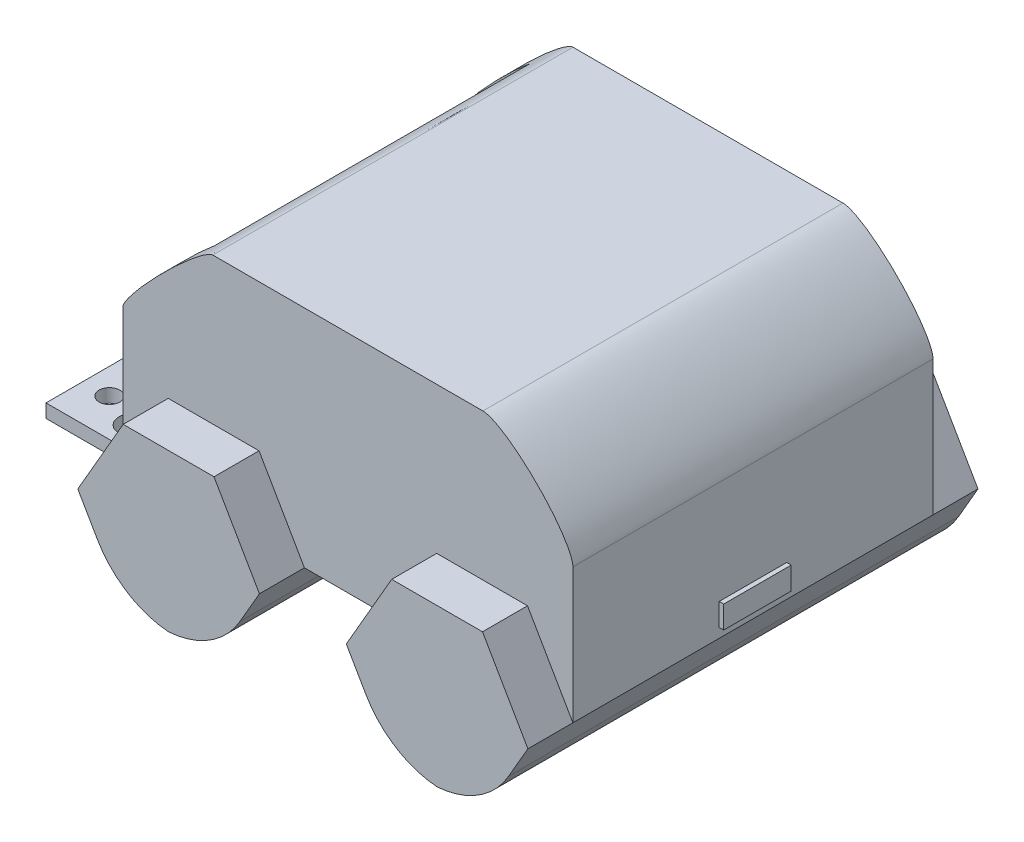
SolidWorks part; units mm, degrees
ref_plane "前基準面" through (0, 0, 0) normal (0, 0, 1) x (1, 0, 0)
ref_plane "上基準面" through (0, 0, 0) normal (0, 1, 0) x (1, 0, 0)
ref_plane "右基準面" through (0, 0, 0) normal (1, 0, 0) x (0, 0, -1)
sketch "草圖1" plane through (0, 0, 0) normal (0, 1, 0) x (1, 0, 0)
  line L1 (-50, 40) -> (50, 40)
  line L2 (-50, 40) -> (-50, -40)
  line L3 (-50, -40) -> (50, -40)
  line L4 (50, 40) -> (50, -40)
  line L5 (-50, 40) -> (50, -40) construction
  line L6 (-50, -40) -> (50, 40) construction
  point P0 (0, 0)
  dimension "D1" = 100
  dimension "D2" = 80
extrude "填料-伸長1" add sketch "草圖1" along normal blind 50
sketch "草圖4" plane through (0, 0, 40) normal (0, 0, 1) x (1, 0, 0)
  line L0 (-50, 0) -> (50, 0) construction
  line L1 (50, 0) -> (39.9127, 17.4718)
  line L2 (39.9127, 17.4718) -> (19.738, 17.4718)
  line L3 (19.738, 17.4718) -> (9.6507, 0)
  line L4 (9.6507, 0) -> (19.738, -17.4718)
  line L5 (19.738, -17.4718) -> (39.9127, -17.4718)
  line L6 (39.9127, -17.4718) -> (50, 0)
  circle A0 centre (29.8253, 0) radius 17.4718 construction
extrude "填料-伸長3" add sketch "草圖4" against normal blind 90 and the other way blind 10
fillet "圓角1" radius 20 1 edges at (50, 50, 0) conic rho 0.2
fillet "圓角2" radius 20 2 edges at (39.9127, -17.4718, 0) (19.738, -17.4718, 0)
sketch "草圖7" plane through (50, 0, 0) normal (1, 0, 0) x (0, 0, -1)
  line L0 (0, -1000) -> (0, 49000) construction
  line L1 (-40, 0) -> (40, 0) construction
  line L3 (-7.5, 7.0981) -> (7.5, 7.0981)
  line L4 (-7.5, 7.0981) -> (-7.5, 2.0981)
  line L5 (-7.5, 2.0981) -> (7.5, 2.0981)
  line L6 (7.5, 7.0981) -> (7.5, 2.0981)
  line L7 (-7.5, 7.0981) -> (7.5, 2.0981) construction
  line L8 (-7.5, 2.0981) -> (7.5, 7.0981) construction
  point P1 (0, 4.5981)
  point P5 (0, 0)
  dimension "D1" = 15
  dimension "D2" = 5
extrude "填料-伸長4" add sketch "草圖7" along normal blind 1
sketch "草圖8" plane through (0, 0, 40) normal (0, 0, 1) x (1, 0, 0)
  line L0 (9.6507, 0) -> (50, 0) construction
  line L1 (50, 30) -> (50, 0) construction
  line L2 (50, 0) -> (39.9127, 17.4718) construction
  line L3 (-50, 0) -> (-9.65, 0) construction
  line L4 (-50, 0) -> (9.6507, 0) construction
  line L6 (-9.65, 0) -> (-19.7375, 17.4721)
  line L7 (-19.7375, 17.4721) -> (-39.9125, 17.4721)
  line L8 (-39.9125, 17.4721) -> (-50, 0)
  line L9 (-50, 0) -> (-39.9125, -17.4721)
  line L10 (-39.9125, -17.4721) -> (-19.7375, -17.4721)
  line L11 (-19.7375, -17.4721) -> (-9.65, 0)
  circle A0 centre (-29.825, 0) radius 17.4721 construction
extrude "填料-伸長5" add sketch "草圖8" along normal blind 10 and the other way blind 90
sketch "草圖9" plane through (-50, 0, 0) normal (-1, 0, 0) x (0, 0, 1)
  line L0 (-40, 50) -> (40, 50) construction
  line L1 (-35, 47) -> (35, 47)
  line L2 (-35, 47) -> (-35, 5)
  line L3 (-35, 5) -> (35, 5)
  line L4 (35, 47) -> (35, 5)
  line L5 (-35, 47) -> (35, 5) construction
  line L6 (-35, 5) -> (35, 47) construction
  line L7 (-40, 0) -> (40, 0) construction
  line L8 (-40, 50) -> (-40, 0) construction
  line L9 (40, 50) -> (40, 0) construction
  point P0 (0, 26)
  dimension "D1" = 3
  dimension "D2" = 5
  dimension "D3" = 5
  dimension "D4" = 5
extrude "除料-伸長1" cut sketch "草圖9" against normal blind 70
sketch "草圖10" plane through (0, 5, 0) normal (0, 1, 0) x (1, 0, 0)
  line L0 (-980, 0) -> (49020, 0) construction
  line L1 (20, 35) -> (20, -35) construction
  line L2 (-15, -965) -> (-15, 49035) construction
  line L3 (20, 35) -> (-50, 35) construction
  line L4 (20, -35) -> (-50, -35) construction
  line L5 (-15, 25.4065) -> (0, 25.4065) construction
  line L6 (-15, 25.4065) -> (-15, 6.8557) construction
  line L7 (-15, 6.8557) -> (0, 6.8557) construction
  line L8 (0, 25.4065) -> (0, 6.8557) construction
  line L9 (14.9508, 25) -> (8.6328, 25)
  line L10 (14.9508, 25) -> (14.9508, -25)
  line L11 (14.9508, -25) -> (8.6328, -25)
  line L12 (8.6328, 25) -> (8.6328, -25)
  point P5 (20, 0)
  point P10 (-15, 35)
  dimension "D1" = 15
  dimension "D2" = 10
  dimension "D3" = 10
extrude "填料-伸長6" add sketch "草圖10" along normal blind 3
sketch "草圖11" plane through (0, 5, 0) normal (0, 1, 0) x (1, 0, 0)
  line L0 (20, 35) -> (20, -35) construction
  line L1 (14.9508, 25) -> (20, 25)
  line L2 (14.9508, 25) -> (14.9508, -25)
  line L3 (14.9508, -25) -> (20, -25)
  line L4 (20, 25) -> (20, -25)
extrude "填料-伸長7" add sketch "草圖11" along normal blind 10
sketch "草圖12" plane through (14.9508, 0, 0) normal (-1, 0, 0) x (0, 0, 1)
  line L0 (25, 15) -> (-25, 15) construction
  line L1 (-21.1605, 14) -> (-18.1605, 14)
  line L2 (-21.1605, 14) -> (-21.1605, 12)
  line L3 (-21.1605, 12) -> (-18.1605, 12)
  line L4 (-18.1605, 14) -> (-18.1605, 12)
  dimension "D1" = 3
  dimension "D2" = 2
  dimension "D3" = 1
extrude "填料-伸長8" add sketch "草圖12" along normal blind 1
sketch "草圖14" plane through (0, 0, 0) normal (0, 1, 0) x (1, 0, 0)
  line L1 (-50, 40) -> (-67.0882, 40)
  line L2 (-50, 40) -> (-50, -39.9756)
  line L3 (-50, -39.9756) -> (-67.0882, -39.9756)
  line L4 (-67.0882, 40) -> (-67.0882, -39.9756)
extrude "填料-伸長9" add sketch "草圖14" along normal blind 3
sketch "草圖15" plane through (0, 3, 0) normal (0, 1, 0) x (1, 0, 0)
  circle A0 centre (-53.1622, -34.5674) radius 3.1274
  circle A1 centre (-61.3484, -22.5611) radius 2.4914
  circle A2 centre (-57.9648, -16.1213) radius 2.2101
  circle A3 centre (-55.7547, -25.0524) radius 1.5139
  circle A4 centre (-61.3484, -31.6204) radius 2.3025
  circle A5 centre (-60.5843, 2.1064) radius 3.7078
  circle A6 centre (-57.9648, 20.2251) radius 2.3359
  circle A7 centre (-55.6289, 12.2572) radius 2.0378
  circle A8 centre (-54.2537, -5.8614) radius 1.3752
  circle A9 centre (-55.6289, 31.4674) radius 2.8525
extrude "除料-伸長2" cut sketch "草圖15" against normal blind 3
fillet "圓角7" radius 20 1 edges at (-50, 50, 0) conic radius 120
fillet "圓角8" radius 20 2 edges at (-19.7375, -17.4721, 0) (-39.9125, -17.4721, 0)
sketch "草圖18" plane through (0, 0, -25) normal (0, 0, -1) x (-1, 0, 0)
  line L0 (-13.9508, 12) -> (-14.9508, 12)
  line L1 (-14.9508, 14) -> (-14.9508, 12) construction
  line L2 (-14.9508, 15) -> (-14.9508, 8) construction
  line L3 (-14.9508, 12) -> (-14.9508, 8)
  line L4 (-14.9508, 8) -> (-8.6328, 8)
  spline S0 degree 3 poles (-13.9508, 12) (-17.0228, 5.424) (-10.669, 10.7569) (-8.6328, 8) knots 0 0 0 0 1 1 1 1
extrude "填料-伸長10" add sketch "草圖18" against normal blind 50
